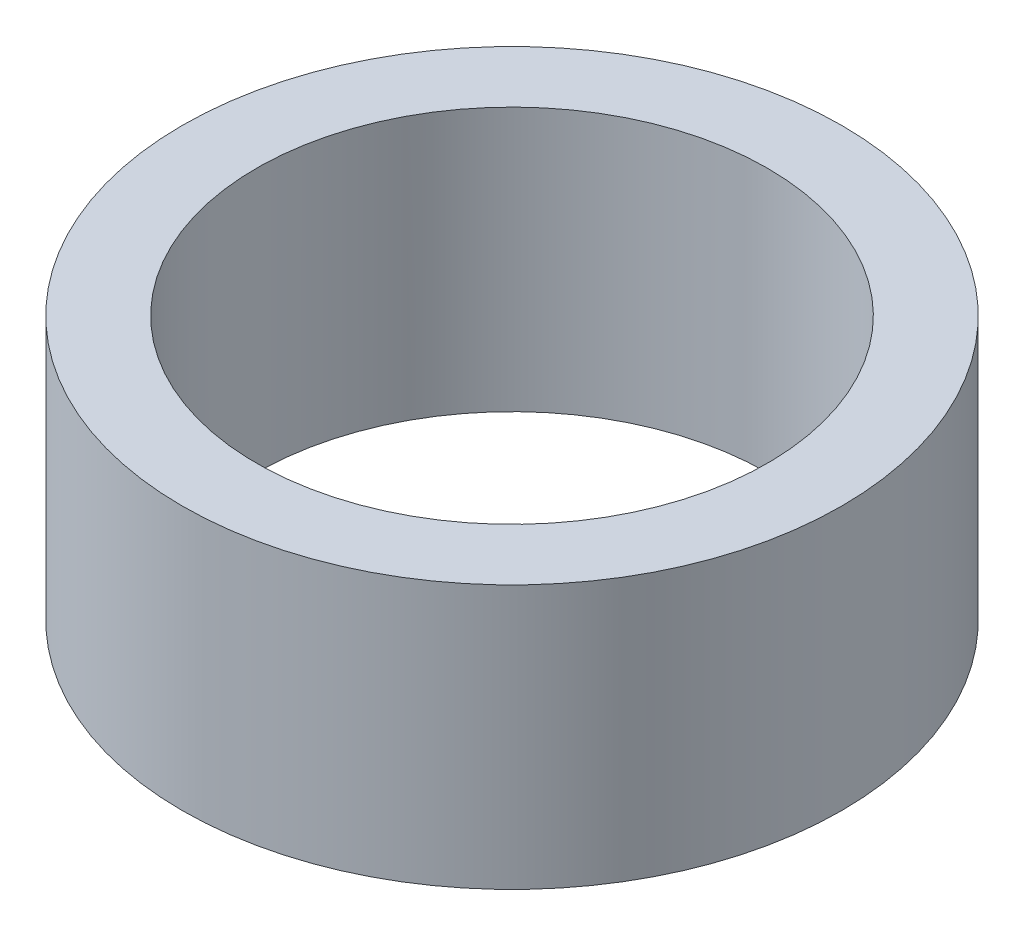
SolidWorks part; units mm, degrees
ref_plane "Front Plane" through (0, 0, 0) normal (0, 0, 1) x (1, 0, 0)
ref_plane "Top Plane" through (0, 0, 0) normal (0, 1, 0) x (1, 0, 0)
ref_plane "Right Plane" through (0, 0, 0) normal (1, 0, 0) x (0, 0, -1)
sketch "Sketch1" plane through (0, 0, 0) normal (0, 1, 0) x (1, 0, 0)
  arc A0 (-7.75, 0) -> (7.75, 0) centre (0, 0) cw
  arc A1 (-10, 0) -> (10, 0) centre (0, 0) cw
  circle A2 centre (0, 0) radius 10
  arc A3 (-7.75, 0) -> (7.75, 0) centre (0, 0) ccw
  point P8 (0, 0)
  point P9 (0, 0)
  point P10 (0, 0)
  point P11 (0, 0)
  point P12 (0, 0)
  dimension "D1" = 7.75
  dimension "D2" = 10
  dimension "D3" = 7.75
  dimension "D4" = 20
extrude "Boss-Extrude1" add sketch "Sketch1" along normal blind 8 contours A2 | A0 A3
